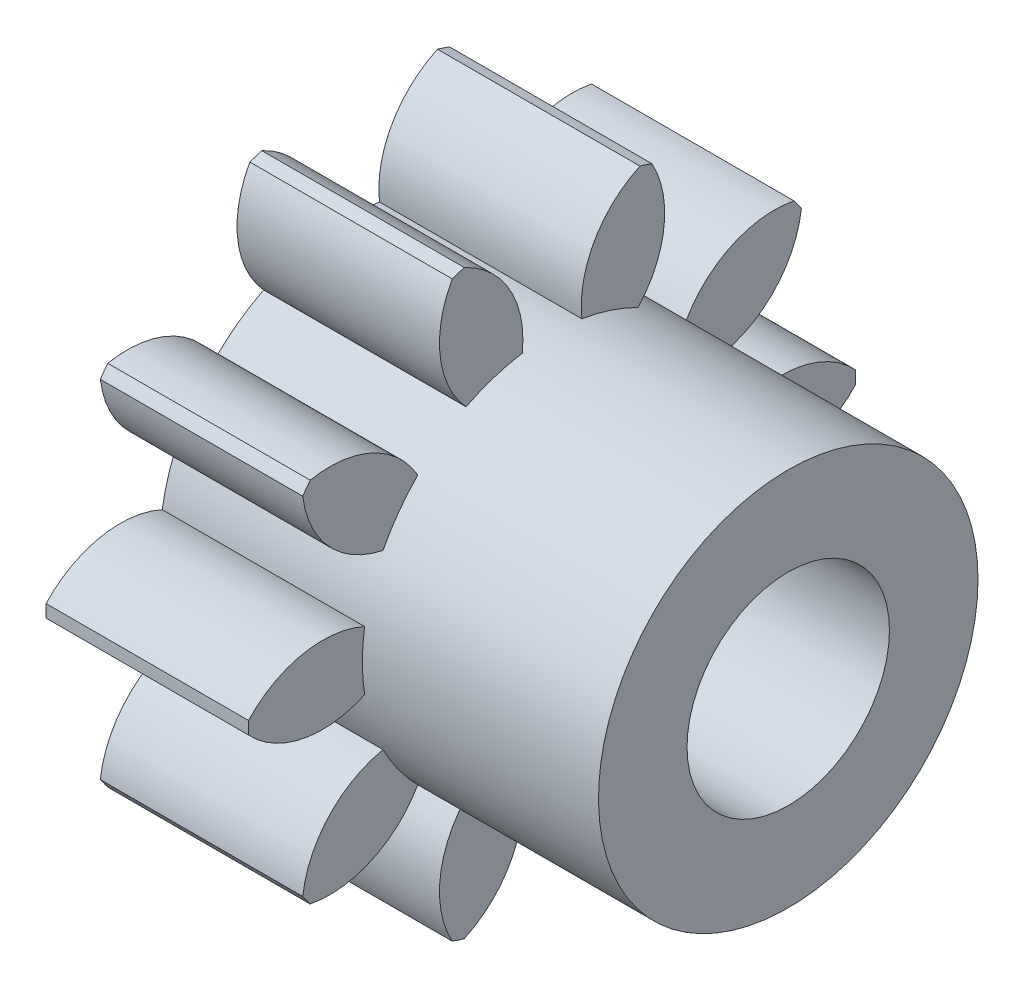
SolidWorks part; units mm, degrees
ref_plane "Plane1" through (0, 0, 0) normal (0, 0, 1) x (1, 0, 0)
ref_plane "Plane2" through (0, 0, 0) normal (0, 1, 0) x (1, 0, 0)
ref_plane "Plane3" through (0, 0, 0) normal (1, 0, 0) x (0, 0, -1)
sketch "HoldingSke" plane through (0, 0, 0) normal (0, 1, 0) x (1, 0, 0)
  line L0 (0, 0) -> (0.6565, -0.1158)
  line L1 (-15, 0) -> (100, 0) construction
  line L2 (0, 0) -> (-2.1039, 2.3779)
  line L3 (0, 0) -> (-11.863, 4.5341)
  line L4 (0, 0) -> (8.5048, 1.4996)
  line L5 (0, 0) -> (-46.8476, -17.4728)
  line L6 (0, 0) -> (-4.9738, -3.3558)
  line L7 (-2.1039, 2.3779) -> (8.6586, 51.2059)
  line L8 (-76.2, 54.61) -> (-75.2, 54.61)
  line L9 (-71.009, 38.7566) -> (-53.1078, 45.2721)
  line L10 (-76.2, 71.12) -> (104.1128, 71.12)
  line L11 (0, 0) -> (-6, 0)
  line L12 (-76.2, 101.6) -> (-76.147, 101.6)
  line L13 (24.9733, 27.94) -> (52.9518, 28.4284)
  line L14 (24.9733, 27.94) -> (24.9743, 27.94)
  line L15 (24.9733, 27.94) -> (100.4006, 29.5858)
  line L16 (-63.627, -1.5) -> (-12.827, -1.5)
  circle A0 centre (0, 0) radius 3
  circle A1 centre (0, 0) radius 5.624
  circle A2 centre (0, 0) radius 37.5
  circle A3 centre (0, 0) radius 3
  dimension "Num_teeth" = 10
  dimension "Pitch_radius" = 180.3128
  dimension "Width" = 6
  dimension "Thickness" = 6
sketch "BasProSke" plane through (0, 0, 0) normal (0, 1, 0) x (1, 0, 0)
  line L0 (-10, 0) -> (60, 0) construction
  line L1 (0, 0) -> (0, 9)
  line L2 (0, 0) -> (6, 0)
  line L3 (6, 0) -> (6, 9)
  line L4 (6, 9) -> (0, 9)
  dimension "Thickness" = 6
  dimension "Diameter" = 18
revolve "Base-Revolve" add sketch "BasProSke" angle 360 about L0
sketch "TooCutSke" plane through (0, 0, 0) normal (1, 0, 0) x (0, 0, -1)
  line L1 (0, 0) -> (0, 107) construction
  line L2 (0, 0) -> (-1.2658, 7.3924) construction
  line L3 (0, 0) -> (-4.5869, 14.117) construction
  line L4 (-1.2658, 7.3924) -> (-2.2934, 7.0585) construction
  arc A0 (0.8839, 5.5541) -> (-0.8839, 5.5541) centre (0, 0) ccw
  arc A1 (2.6378, 8.6313) -> (-2.6378, 8.6313) centre (0, 0) ccw
  circle A2 centre (0, 0) radius 7.5 construction
  circle A3 centre (0, 0) radius 7.0477 construction
  arc A4 (-0.8839, 5.5541) -> (-2.6378, 8.6313) centre (-3.8646, 5.8936) ccw
  arc A5 (2.6378, 8.6313) -> (0.8839, 5.5541) centre (3.8646, 5.8936) ccw
extrude "ToothCut" cut sketch "TooCutSke" along normal through all
fillet "Breaks" [suppressed] radius 0.03 tangent propagation no
fillet "RootFillets" [suppressed] radius 0.376
pattern_circular "TeethCuts" count 10 every 36 about axis through (-10, 0, 0) along (1, 0, 0) of "ToothCut", "RootFillets", "Breaks"
sketch "HubNeaOneSke" plane through (0, 0, 0) normal (-1, 0, 0) x (0, 0, 1)
  circle A0 centre (0, 0) radius 5.624
  dimension "Diameter" = 11.248
extrude "HubNearOne" [suppressed] add sketch "HubNeaOneSke" along normal blind 44.0001
sketch "HubNeaBotSke" plane through (0, 0, 0) normal (-1, 0, 0) x (0, 0, 1)
  circle A0 centre (0, 0) radius 5.624
  dimension "Diameter" = 11.248
extrude "HubNearBoth" [suppressed] add sketch "HubNeaBotSke" along normal blind 22
ref_plane "FarPln" through (6, 0, 0) normal (1, 0, 0) x (0, 0, -1)
sketch "HubFarSke" plane through (6, 0, 0) normal (1, 0, 0) x (0, 0, -1)
  circle A0 centre (0, 0) radius 5.624
  dimension "Diameter" = 11.248
extrude "HubFar" [suppressed] add sketch "HubFarSke" along normal blind 22
sketch "BorSke" plane through (0, 0, 0) normal (1, 0, 0) x (0, 0, -1)
  circle A0 centre (0, 0) radius 3
  dimension "Diameter" = 6
extrude "Bore" cut sketch "BorSke" along normal mid plane 100.0001
sketch "KeySke" plane through (0, 0, 0) normal (1, 0, 0) x (0, 0, -1)
  line L0 (-1, 0) -> (-1, 4)
  line L1 (-1, 4) -> (1, 4)
  line L2 (1, 4) -> (1, 0)
  line L3 (0, 0) -> (0, 34) construction
  line L4 (-1, 0) -> (1, 0)
  dimension "Width" = 2
extrude "Keyway" [suppressed] cut sketch "KeySke" along normal mid plane 100.0001
pattern_circular "Keyway2" [suppressed] count 2 every 90 about axis through (-10, 0, 0) along (1, 0, 0) reverse direction yes
sketch "Sketch1" plane through (6, 0, 0) normal (1, 0, 0) x (0, 0, -1)
  circle A0 centre (0, 0) radius 5.624
  circle M2 centre (0, 0) radius 3
  arc M4 (5.5554, 0.8757) -> (5.0091, 2.5569) centre (0, 0) ccw
  arc M8 (3.9797, 3.9738) -> (2.5496, 5.0129) centre (0, 0) ccw
  arc M12 (0.8839, 5.5541) -> (-0.8839, 5.5541) centre (0, 0) ccw
  arc M16 (-2.5496, 5.0129) -> (-3.9797, 3.9738) centre (0, 0) ccw
  arc M20 (-5.0091, 2.5569) -> (-5.5554, 0.8757) centre (0, 0) ccw
  arc M24 (-5.5554, -0.8757) -> (-5.0091, -2.5569) centre (0, 0) ccw
  arc M28 (-3.9797, -3.9738) -> (-2.5496, -5.0129) centre (0, 0) ccw
  arc M32 (-0.8839, -5.5541) -> (0.8839, -5.5541) centre (0, 0) ccw
  arc M36 (2.5496, -5.0129) -> (3.9797, -3.9738) centre (0, 0) ccw
  arc M40 (5.0091, -2.5569) -> (5.5554, -0.8757) centre (0, 0) ccw
extrude "Boss-Extrude1" add sketch "Sketch1" along normal blind 7 contours A0 M4 M8 M12 M16 M20 M24 M28 M32 M36 M40 M2 region at (6, -0.4268, -5.4482)
equation "' \"Module@HoldingSke\" = 6.35"
equation "' \"Num_teeth@HoldingSke\" = 12"
equation "' \"Ap@HoldingSke\" =  20"
equation "' \"Ap@HoldingSke\" = 20"
equation "' \"Width@HoldingSke\" = 0.5 * 25.4"
equation "' \"Hub_dia@HoldingSke\"= 1 * 25.4"
equation "' \"Hub_dia@HoldingSke\" = 1 * 25.4"
equation "' \"Overall_len@HoldingSke\" = 1.0 * 25.4"
equation "' \"Bore@HoldingSke\" = 0.75 * 25.4"
equation "' \"T_dim@HoldingSke\" = 0.1 * 25.4"
equation "' \"Width@KeySke\" = 0.25 * 25.4"
equation "' \"Show_teeth@HoldingSke\" = 13"
equation "' \"Backlash@HoldingSke\" = 0.009 * 25.4"
equation "' \"Addendum_fac@HoldingSke\" = 1.0"
equation "' \"Dedendum_fac@HoldingSke\" = 1.25"
equation "' \"Dedendum_add@HoldingSke\" = 0.00005 * 25.4"
equation "' \"Clearance_fac@HoldingSke\" = 0.25"
equation "\"Pitch@HoldingSke\" = 1 / \"Module@HoldingSke\""
equation "\"Overcut_dia@TooCutSke\" = (\"Num_teeth@HoldingSke\" + 2 * \"Addendum_fac@HoldingSke\") / \"Pitch@HoldingSke\" + 0.002 * 25.4"
equation "\"Pitch_dia@TooCutSke\" = \"Num_teeth@HoldingSke\" / \"Pitch@HoldingSke\""
equation "\"Base_dia@TooCutSke\" = \"Num_teeth@HoldingSke\" / \"Pitch@HoldingSke\" * cos((\"Ap@HoldingSke\"  * 3.14159265 / 180))"
equation "\"Root_dia@TooCutSke\" = (\"Num_teeth@HoldingSke\" + 2) / \"Pitch@HoldingSke\" - 2 * (\"Addendum_fac@HoldingSke\" + \"Dedendum_fac@HoldingSke\") / \"Pitch@HoldingSke\" - \"Dedendum_add@HoldingSke\" * 2"
equation "\"Half_ang@TooCutSke\" = 180 / \"Num_teeth@HoldingSke\""
equation "\"Half_CT@TooCutSke\" = \"Num_teeth@HoldingSke\" / \"Pitch@HoldingSke\" * sin((3.14159265 / 2 / \"Num_teeth@HoldingSke\")) / 2 - 7 * \"Backlash@HoldingSke\" / 4"
equation "\"Flank_rad@TooCutSke\" = \"Num_teeth@HoldingSke\" / \"Pitch@HoldingSke\" / 5"
equation "\"Radius@RootFillets\" = \"Clearance_fac@HoldingSke\" / \"Pitch@HoldingSke\" + \"Dedendum_add@HoldingSke\""
equation "\"Break_rad@Breaks\" = 0.02 / \"Pitch@HoldingSke\""
equation "\"Thickness@HoldingSke\" = \"Width@HoldingSke\""
equation "\"OAL@HoldingSke\" = \"Thickness@HoldingSke\""
equation "\"MHD@HoldingSke\" = (\"Num_teeth@HoldingSke\" + 2) / \"Pitch@HoldingSke\" - 2 * (\"Addendum_fac@HoldingSke\" + \"Dedendum_fac@HoldingSke\")  / \"Pitch@HoldingSke\" - \"Dedendum_add@HoldingSke\" * 2"
equation "\"MBD@HoldingSke\" = (\"Num_teeth@HoldingSke\" + 2) / \"Pitch@HoldingSke\" - 2 * (\"Addendum_fac@HoldingSke\" + \"Dedendum_fac@HoldingSke\")  / \"Pitch@HoldingSke\" - \"Dedendum_add@HoldingSke\" * 2 - 0.002 * 25.4"
equation "\"MHD@HoldingSke\" = ((sgn( \"MHD@HoldingSke\" - \"Hub_dia@HoldingSke\" )-1)*( \"MHD@HoldingSke\" - \"Hub_dia@HoldingSke\" ))/-2+ \"Hub_dia@HoldingSke\""
equation "\"MBD@HoldingSke\" = ((sgn( \"MBD@HoldingSke\" - \"Bore@HoldingSke\" )-1)*( \"MBD@HoldingSke\" - \"Bore@HoldingSke\" ))/-2+ \"Bore@HoldingSke\""
equation "\"OAL@HoldingSke\" = ((sgn( \"OAL@HoldingSke\" - \"Overall_len@HoldingSke\" )+1)*( \"OAL@HoldingSke\" - \"Overall_len@HoldingSke\" ))/2 + \"Overall_len@HoldingSke\" + 0.000002 * 25.4"
equation "\"Num_teeth@TeethCuts\" = int( \"Show_teeth@HoldingSke\" ) + 1"
equation "\"Num_teeth@TeethCuts\" = ((sgn( \"Num_teeth@TeethCuts\" - \"Num_teeth@HoldingSke\" )-1)*( \"Num_teeth@TeethCuts\" - \"Num_teeth@HoldingSke\" ))/-2+ \"Num_teeth@HoldingSke\""
equation "\"Num_teeth@TeethCuts\" = ((sgn( \"Num_teeth@TeethCuts\" - 2.0)+1)*( \"Num_teeth@TeethCuts\" - 2.0))/2 +2.0"
equation "\"Angle@TeethCuts\" = 360.0 / \"Num_teeth@HoldingSke\""
equation "\"Diameter@BasProSke\" = (\"Num_teeth@HoldingSke\" + 2 * \"Addendum_fac@HoldingSke\") / \"Pitch@HoldingSke\""
equation "\"Thickness@BasProSke\"  = \"Thickness@HoldingSke\""
equation "' \"Fillet_rad@BasProSke\" =  \"Thickness@HoldingSke\" * 0.05"
equation "' \"Fillet_rad@BasProSke\" = \"Thickness@HoldingSke\" * 0.05"
equation "\"MHD@HoldingSke\" = ((sgn( \"MHD@HoldingSke\" - \"Root_dia@TooCutSke\" )-1)*( \"MHD@HoldingSke\" - \"Root_dia@TooCutSke\" ))/-2+ \"Root_dia@TooCutSke\""
equation "\"Diameter@HubNeaOneSke\" = \"MHD@HoldingSke\""
equation "\"Length@HubNearOne\" = \"OAL@HoldingSke\" - \"Thickness@BasProSke\""
equation "\"Diameter@HubNeaBotSke\" = \"MHD@HoldingSke\""
equation "\"Length@HubNearBoth\" = ( \"OAL@HoldingSke\" - \"Thickness@BasProSke\" ) / 2.0"
equation "\"Thickness@FarPln\" = \"Thickness@BasProSke\""
equation "\"Diameter@HubFarSke\" = \"MHD@HoldingSke\""
equation "\"Length@HubFar\" = ( \"OAL@HoldingSke\" - \"Thickness@BasProSke\" ) / 2.0"
equation "\"Diameter@BorSke\" = \"MBD@HoldingSke\""
equation "\"D1@Bore\" = \"OAL@HoldingSke\" * 2.0"
equation "\"D1@Keyway\" = \"OAL@HoldingSke\" * 2.0"
equation "\"Offset@KeySke\" = \"T_dim@HoldingSke\" + \"MBD@HoldingSke\" / 2.0"
